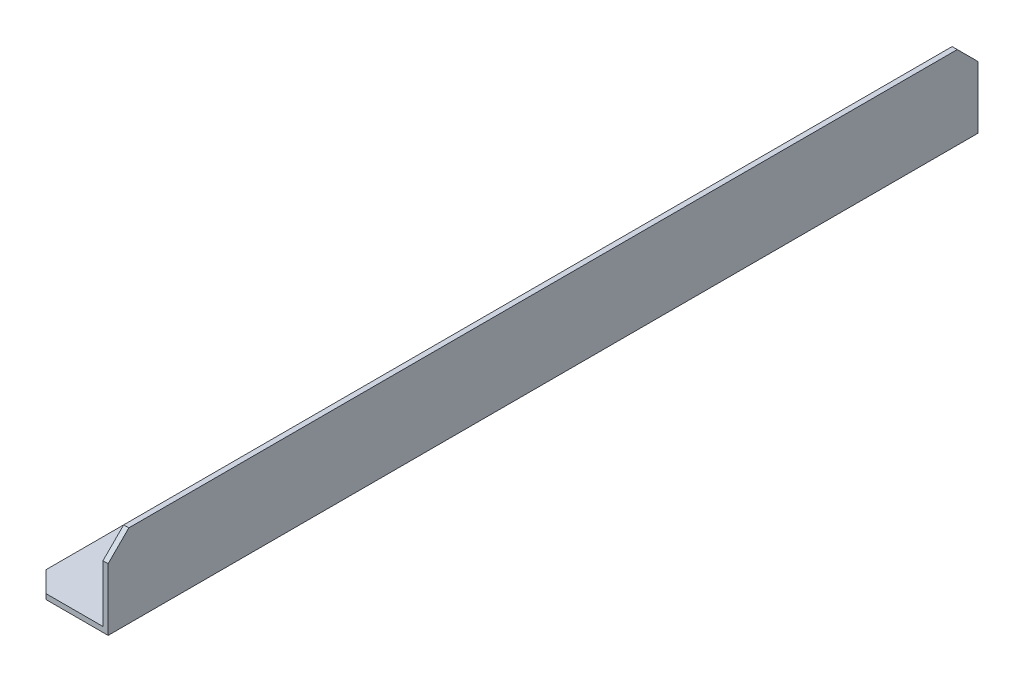
SolidWorks part; units mm, degrees
material "6063-T5"
ref_plane "Front Plane" through (0, 0, 0) normal (0, 0, 1) x (1, 0, 0)
ref_plane "Top Plane" through (0, 0, 0) normal (0, 1, 0) x (1, 0, 0)
ref_plane "Right Plane" through (0, 0, 0) normal (1, 0, 0) x (0, 0, -1)
sketch "Sketch2" plane through (0, 0, 0) normal (0, 0, 1) x (1, 0, 0)
  line L0 (0, 0) -> (0, 50.8)
  line L1 (0, 0) -> (-50.8, 0)
  line L2 (-3.175, 3.175) -> (-3.175, 50.8)
  line L3 (-3.175, 3.175) -> (-50.8, 3.175)
  line L4 (0, 50.8) -> (-3.175, 50.8)
  line L5 (-50.8, 0) -> (-50.8, 3.175)
  dimension "D1" = 50.8
  dimension "D2" = 50.8
  dimension "D3" = 3.175
extrude "Boss-Extrude1" add sketch "Sketch2" against normal blind 533.4
chamfer "Chamfer1" distance 12.7 angle 45 4 edges at (-50.8, 1.5875, -533.4) (-1.5875, 50.8, -533.4) (-1.5875, 50.8, 0) (-50.8, 1.5875, 0)
hole_wizard "CSK for #8 Flat Head Machine Screw (100)1" positions "Sketch3" profile "Sketch4" countersink size "#8" standard "ANSI Inch" end condition through all
sketch "Sketch3" plane through (0, 3.175, 0) normal (0, 1, 0) x (1, 0, 0)
  line L0 (-50.8, 266.7) -> (-3.175, 266.7) construction
  line L1 (-50.8, 520.7) -> (-50.8, 12.7) construction
  line L2 (-3.175, 533.4) -> (-3.175, 0) construction
  line L4 (-26.9875, 266.7) -> (-26.9875, 0) construction
  line L5 (-3.175, 0) -> (-38.1, 0) construction
  point P15 (-26.9875, 38.1)
  point P26 (-26.9875, 152.4)
  point P27 (-26.9875, 266.7)
  point P28 (-26.9875, 381)
  point P29 (-26.9875, 495.3)
  point P32 (-26.9875, 266.7)
  dimension "D3" = 114.3
  dimension "D2" = 5
sketch "Sketch4" plane through (-26.9875, 3.175, -495.3) normal (1, 0, 0) x (0, 0, 1)
  line L0 (0, 0) -> (0, 3.175)
  line L1 (0, 3.175) -> (2.4574, 3.175)
  line L2 (2.4574, 3.175) -> (2.4574, 1.4759)
  line L3 (2.4574, 1.4759) -> (4.2164, 0)
  line L5 (4.2164, 0) -> (0, 0)
  line L6 (-2.4574, 1.4759) -> (-4.2164, 0) construction
  line L11 (0, -6.35) -> (0, 107.95) construction
  dimension "Thru Hole Dia." = 4.9149
  dimension "Thru Hole Depth" = 3.175
  dimension "Near C'Sink Dia." = 8.4328
  dimension "Near C'Sink Angle" = 100
equation "\"D2@Sketch2\"=\"D1@Sketch2\""
